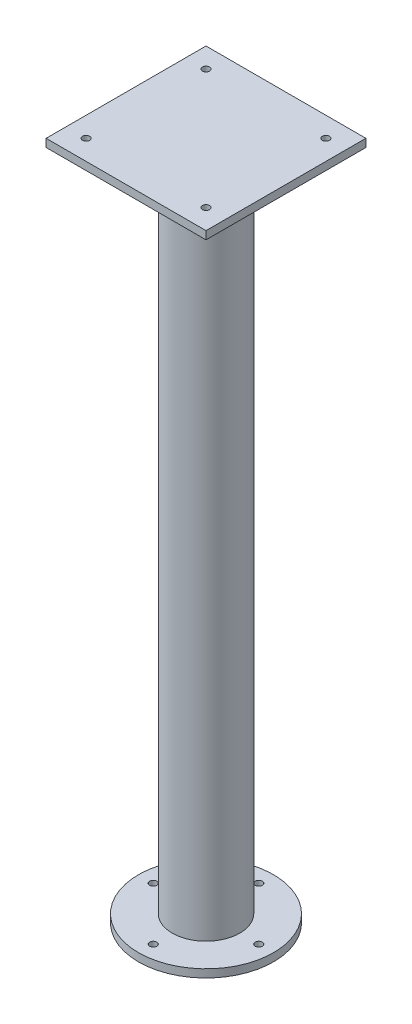
SolidWorks part; units mm, degrees
ref_plane "Front Plane" through (0, 0, 0) normal (0, 0, 1) x (1, 0, 0)
ref_plane "Top Plane" through (0, 0, 0) normal (0, 1, 0) x (1, 0, 0)
ref_plane "Right Plane" through (0, 0, 0) normal (1, 0, 0) x (0, 0, -1)
sketch "Sketch1" plane through (0, 0, 0) normal (0, 1, 0) x (1, 0, 0)
  circle A0 centre (0, 0) radius 66 construction
  circle A1 centre (0, 0) radius 84.5
  circle A2 centre (0, -66) radius 4.5
  circle A3 centre (66, 0) radius 4.5
  circle A4 centre (-66, 0) radius 4.5
  circle A5 centre (0, 66) radius 4.5
  dimension "D1" = 169
  dimension "D2" = 132
  dimension "D3" = 9
  dimension "D4" = 9
  dimension "D5" = 9
  dimension "D6" = 9
extrude "Boss-Extrude4" add sketch "Sketch1" along normal blind 10
sketch "Sketch2" plane through (0, 10, 0) normal (0, 1, 0) x (1, 0, 0)
  circle A0 centre (0, 0) radius 42.25
  dimension "D1" = 84.5
extrude "Boss-Extrude5" add sketch "Sketch2" along normal blind 830
sketch "Sketch4" plane through (0, 840, 0) normal (0, 1, 0) x (1, 0, 0)
  line L1 (-100, -100) -> (100, -100)
  line L2 (-100, -100) -> (-100, 100)
  line L3 (-100, 100) -> (100, 100)
  line L4 (100, -100) -> (100, 100)
  line L5 (-100, -100) -> (100, 100) construction
  line L6 (-100, 100) -> (100, -100) construction
  line L11 (-82.9569, -82.9569) -> (82.9569, 82.9569) construction
  line L12 (-82.9569, 82.9569) -> (82.9569, -82.9569) construction
  point P0 (0, 0)
  point P6 (0, 0)
  dimension "D1" = 200
  dimension "D2" = 200
extrude "Boss-Extrude6" add sketch "Sketch4" along normal blind 10
sketch "Sketch5" plane through (0, 850, 0) normal (0, 1, 0) x (1, 0, 0)
  line L1 (-75, -75) -> (75, -75)
  line L2 (-75, -75) -> (-75, 75)
  line L3 (-75, 75) -> (75, 75)
  line L4 (75, -75) -> (75, 75)
  line L5 (-75, -75) -> (75, 75) construction
  line L6 (-75, 75) -> (75, -75) construction
  circle A0 centre (75, -75) radius 4.5
  circle A1 centre (-75, -75) radius 4.5
  circle A2 centre (-75, 75) radius 4.5
  circle A3 centre (75, 75) radius 4.5
  point P0 (0, 0)
  dimension "D3" = 9
  dimension "D4" = 9
  dimension "D5" = 9
  dimension "D6" = 9
  dimension "D1" = 150
  dimension "D2" = 150
extrude "Cut-Extrude1" cut sketch "Sketch5" against normal through all contours L2 A1 L1 | L1 A1 L2 | L3 A2 L2 | L2 A2 L3 | L4 A3 L3 | L3 A3 L4 | L1 A0 L4 | L4 A0 L1 region at (-73.0901, 850, 73.0901) region at (-75.6366, 850, 75.6366) region at (73.0901, 850, 73.0901) region at (75.6366, 850, 75.6366) region at (-75.6366, 850, -75.6366) region at (-73.0901, 850, -73.0901) region at (73.0901, 850, -73.0901) region at (75.6366, 850, -75.6366)
sketch "Sketch6" plane through (0, 0, 0) normal (0, 0, 1) x (1, 0, 0)
  line L0 (-100, 850) -> (100, 850) construction
  point P0 (0, 850)
